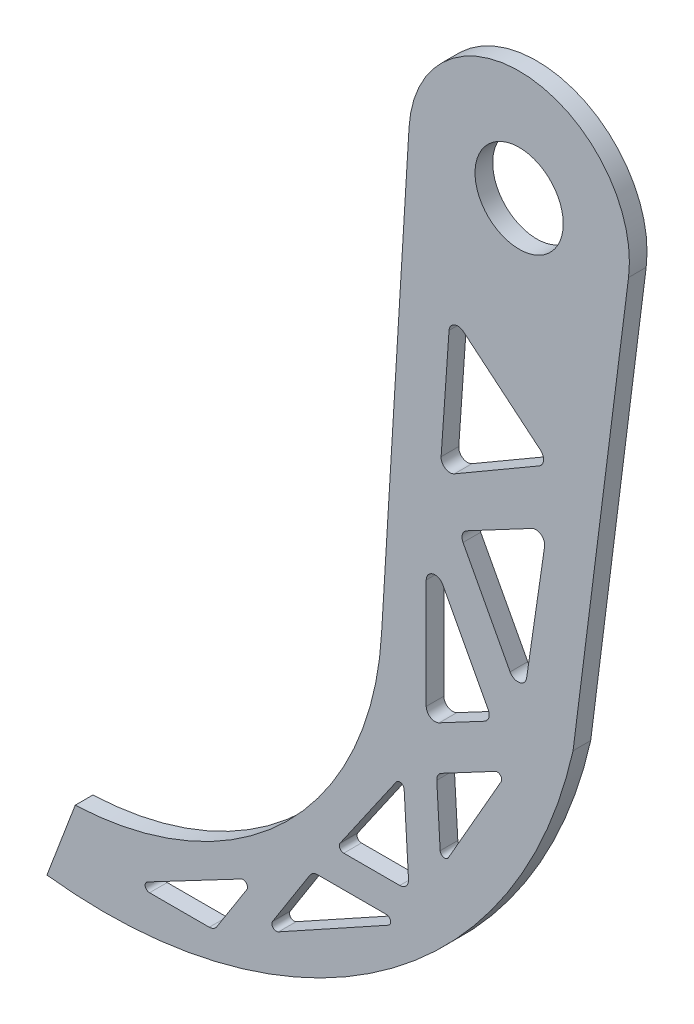
SolidWorks part; units mm, degrees
material "Stainless Steel (ferritic)"
ref_plane "Front Plane" through (0, 0, 0) normal (0, 0, 1) x (1, 0, 0)
ref_plane "Top Plane" through (0, 0, 0) normal (0, 1, 0) x (1, 0, 0)
ref_plane "Right Plane" through (0, 0, 0) normal (1, 0, 0) x (0, 0, -1)
sketch "Sketch1" plane through (0, 0, 0) normal (0, 0, 1) x (1, 0, 0)
  line L1 (-24.9539, 1.5169) -> (-31.1753, -100.8253)
  line L2 (24.8015, -3.1445) -> (12.2236, -102.3503)
  line L3 (-100.6374, -169.4674) -> (-107.0496, -186.3951)
  line L6 (6.347, -61.5371) -> (-13.6551, -72.1619)
  line L7 (-13.6551, -72.1619) -> (0.81, -99.3938)
  line L8 (0.81, -99.3938) -> (6.347, -61.5371)
  line L9 (-21.0647, -77.437) -> (-6.0794, -105.6482)
  line L10 (-6.0794, -105.6482) -> (-21.0647, -113.6081)
  line L11 (-21.0647, -113.6081) -> (-21.0647, -77.437)
  line L18 (-26.2343, -155.6508) -> (-46.8245, -155.6508)
  line L19 (-46.8245, -155.6508) -> (-57.9967, -173.2028)
  line L20 (-57.9967, -173.2028) -> (-26.2343, -155.6508)
  line L21 (-59.7119, -163.4105) -> (-69.1484, -178.2355)
  line L22 (-69.1484, -178.2355) -> (-87.8295, -178.2355)
  line L23 (-87.8295, -178.2355) -> (-59.7119, -163.4105)
  line L24 (-26.2343, -126.1753) -> (-24.9539, -148.4468)
  line L25 (-24.9539, -148.4468) -> (-41.6637, -148.4468)
  line L26 (-41.6637, -148.4468) -> (-26.2343, -126.1753)
  line L27 (-18.7473, -122.3052) -> (-2.3742, -113.6081)
  line L28 (-2.3742, -113.6081) -> (-17.7073, -140.3954)
  line L29 (-17.7073, -140.3954) -> (-18.7473, -122.3052)
  line L30 (-17.9496, -63.3379) -> (7.0163, -48.83)
  line L31 (7.0163, -48.83) -> (-15.6206, -29.9885)
  line L32 (-15.6206, -29.9885) -> (-17.9496, -63.3379)
  circle A0 centre (0, 0) radius 10
  arc A1 (24.8015, -3.1445) -> (-24.9539, 1.5169) centre (0, 0) ccw
  arc A2 (12.2236, -102.3503) -> (-107.0496, -186.3951) centre (-93.9061, -78.3914) cw
  arc A3 (-31.1753, -100.8253) -> (-100.6374, -169.4674) centre (-103.5763, -97.0263) cw
  circle A4 centre (0, 0) radius 25 construction
  dimension "D1" = 15
  dimension "D3" = 360
  dimension "D4" = 0
  dimension "D5" = 0
  dimension "D7" = 360
extrude "Boss-Extrude1" add sketch "Sketch1" along normal blind 4 contours L2 A2 L3 A3 L1 A1
extrude "Cut-Extrude2" cut sketch "Sketch1<3>" along normal blind 19.5 contours A0
sketch "Sketch1<3>" plane through (0, 0, 0) normal (0, 0, 1) x (1, 0, 0) same geometry as "Sketch1"
extrude "Cut-Extrude3" cut sketch "Sketch1<4>" along normal blind 59.5 contours L6 L7 L8 | L30 L31 L32 | L18 L19 L20 | L24 L25 L26 | L27 L28 L29 | L9 L10 L11 | L23 L21 L22
sketch "Sketch1<4>" plane through (0, 0, 0) normal (0, 0, 1) x (1, 0, 0) same geometry as "Sketch1"
fillet "Fillet2" radius 2 9 edges at (-6.0794, -105.6482, 2) (-21.0647, -113.6081, 2) (-21.0647, -77.437, 2) (6.347, -61.5371, 2) (0.81, -99.3938, 2) (-13.6551, -72.1619, 2) (-15.6206, -29.9885, 2) (7.0163, -48.83, 2) (-17.9496, -63.3379, 2)
fillet "Fillet9" radius 2 4 edges at (-69.1484, -178.2355, 2) (-46.8245, -155.6508, 2) (-24.9539, -148.4468, 2) (-18.7473, -122.3052, 2)
fillet "Fillet10" radius 1 8 edges at (-59.7119, -163.4105, 2) (-87.8295, -178.2355, 2) (-57.9967, -173.2028, 2) (-26.2343, -155.6508, 2) (-41.6637, -148.4468, 2) (-17.7073, -140.3954, 2) (-26.2343, -126.1753, 2) (-2.3742, -113.6081, 2)
